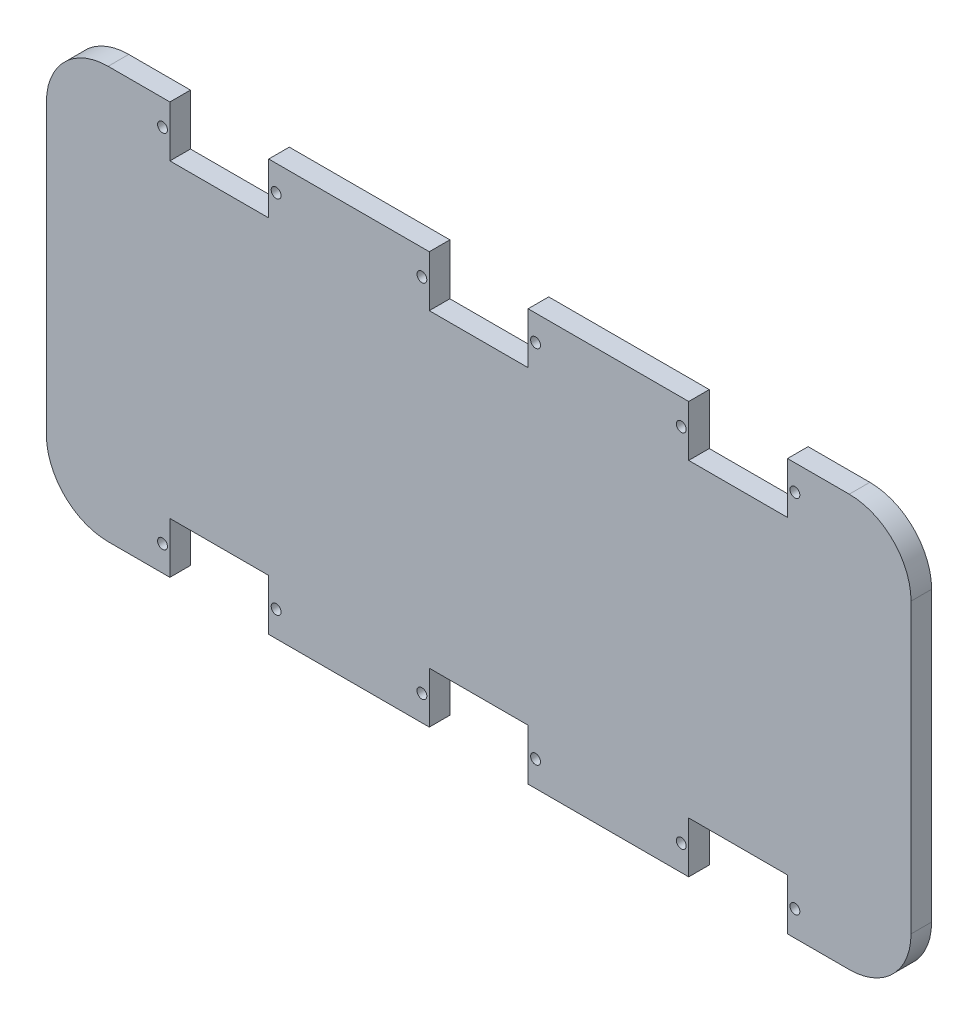
SolidWorks part; units mm, degrees
ref_plane "Front Plane" through (0, 0, 0) normal (0, 0, 1) x (1, 0, 0)
ref_plane "Top Plane" through (0, 0, 0) normal (0, 1, 0) x (1, 0, 0)
ref_plane "Right Plane" through (0, 0, 0) normal (1, 0, 0) x (0, 0, -1)
sketch "Sketch1" plane through (0, 0, 0) normal (0, 0, 1) x (1, 0, 0)
  line L1 (-90, -50) -> (90, -50)
  line L2 (-105, -35) -> (-105, 35)
  line L3 (-90, 50) -> (90, 50)
  line L4 (105, -35) -> (105, 35)
  line L5 (-105, -50) -> (105, 50) construction
  line L6 (-105, 50) -> (105, -50) construction
  arc A0 (-105, -35) -> (-90, -50) centre (-90, -35) ccw
  arc A1 (90, -50) -> (105, -35) centre (90, -35) ccw
  arc A2 (105, 35) -> (90, 50) centre (90, 35) ccw
  arc A3 (-90, 50) -> (-105, 35) centre (-90, 35) ccw
  point P0 (0, 0)
  dimension "D3" = 15
  dimension "D1" = 210
  dimension "D2" = 100
extrude "Boss-Extrude2" add sketch "Sketch1" along normal blind 5
sketch "Sketch2" plane through (0, 0, 5) normal (0, 0, 1) x (1, 0, 0)
  line L0 (-105, 0) -> (-75, 0) construction
  line L1 (-105, 35) -> (-105, -35) construction
  line L2 (-75, 0) -> (-51, 0) construction
  line L3 (-51, 0) -> (-12, 0) construction
  line L4 (-12, 0) -> (12, 0) construction
  line L5 (12, 0) -> (51, 0) construction
  line L6 (51, 0) -> (75, 0) construction
  line L7 (-75, 0) -> (-75, 50) construction
  line L8 (90, 50) -> (-90, 50) construction
  line L9 (-51, 0) -> (-51, 50) construction
  line L10 (-12, 0) -> (-12, 50) construction
  line L11 (12, 0) -> (12, 50) construction
  line L12 (51, 0) -> (51, 50) construction
  line L13 (75, 0) -> (75, 50) construction
  line L14 (-75, 0) -> (-75, -50) construction
  line L15 (-90, -50) -> (90, -50) construction
  line L16 (-51, 0) -> (-51, -50) construction
  line L17 (-12, 0) -> (-12, -50) construction
  line L18 (12, 0) -> (12, -50) construction
  line L19 (51, 0) -> (51, -50) construction
  line L20 (75, 0) -> (75, -50) construction
  line L21 (51, -37.6) -> (75, -37.6)
  line L22 (-75, 50) -> (-51, 50)
  line L23 (-75, 50) -> (-75, 37.6)
  line L24 (-75, 37.6) -> (-51, 37.6)
  line L25 (-51, 50) -> (-51, 37.6)
  line L26 (-12, 50) -> (12, 50)
  line L27 (-12, 50) -> (-12, 37.6)
  line L28 (-12, 37.6) -> (12, 37.6)
  line L29 (12, 50) -> (12, 37.6)
  line L30 (51, 50) -> (75, 50)
  line L31 (51, 50) -> (51, 37.6)
  line L32 (51, 37.6) -> (75, 37.6)
  line L33 (75, 50) -> (75, 37.6)
  line L34 (75, -50) -> (75, -37.6)
  line L35 (51, -50) -> (75, -50)
  line L36 (51, -50) -> (51, -37.6)
  line L37 (-12, -37.6) -> (12, -37.6)
  line L38 (12, -50) -> (12, -37.6)
  line L39 (-12, -50) -> (12, -50)
  line L40 (-12, -50) -> (-12, -37.6)
  line L41 (-75, -37.6) -> (-51, -37.6)
  line L42 (-51, -50) -> (-51, -37.6)
  line L43 (-75, -50) -> (-51, -50)
  line L44 (-75, -50) -> (-75, -37.6)
  dimension "D1" = 30
  dimension "D2" = 24
  dimension "D3" = 39
  dimension "D4" = 24
  dimension "D5" = 39
  dimension "D6" = 24
  dimension "D7" = 12.4
  dimension "D8" = 12.4
extrude "Cut-Extrude1" cut sketch "Sketch2" against normal blind 5
sketch "Sketch3" plane through (0, 0, 5) normal (0, 0, 1) x (1, 0, 0)
  line L0 (-51, 50) -> (-51, 37.6) construction
  line L1 (-105, 0) -> (105, 0) construction
  line L2 (-75, 50) -> (-75, 37.6) construction
  line L3 (-105, 35) -> (-105, -35) construction
  line L4 (-75, 43.8) -> (-76.8, 43.8) construction
  line L5 (-51, 43.8) -> (-49.2, 43.8) construction
  line L6 (105, -35) -> (105, 35) construction
  circle A0 centre (-76.8, 43.8) radius 1.2
  circle A1 centre (-49.2, 43.8) radius 1.2
  circle A2 centre (-13.8, 43.8) radius 1.2
  circle A3 centre (13.8, 43.8) radius 1.2
  circle A4 centre (49.2, 43.8) radius 1.2
  circle A5 centre (76.8, 43.8) radius 1.2
  circle A6 centre (-76.8, -43.8) radius 1.2
  circle A7 centre (-49.2, -43.8) radius 1.2
  circle A8 centre (-13.8, -43.8) radius 1.2
  circle A9 centre (13.8, -43.8) radius 1.2
  circle A10 centre (49.2, -43.8) radius 1.2
  circle A11 centre (76.8, -43.8) radius 1.2
  dimension "D2" = 1.8
  dimension "D3" = 3
  dimension "D1" = 1.8
extrude "Cut-Extrude2" cut sketch "Sketch3" against normal blind 5
